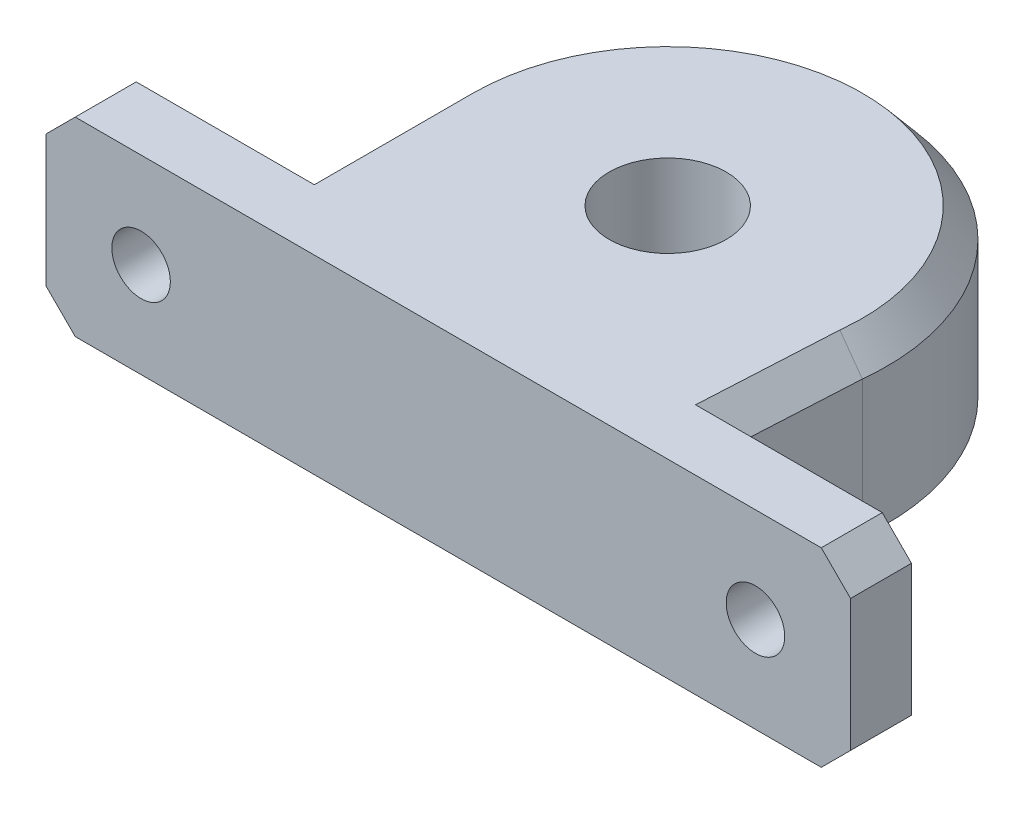
SolidWorks part; units mm, degrees
ref_plane "Płaszczyzna przednia" through (0, 0, 0) normal (0, 0, 1) x (1, 0, 0)
ref_plane "Płaszczyzna górna" through (0, 0, 0) normal (0, 1, 0) x (1, 0, 0)
ref_plane "Płaszczyzna prawa" through (0, 0, 0) normal (1, 0, 0) x (0, 0, -1)
sketch "Szkic1" plane through (0, 0, 0) normal (0, 1, 0) x (1, 0, 0)
  circle A0 centre (0, 15) radius 15
  circle A1 centre (0, 15) radius 4
extrude "Dodanie-wyciągnięcie1" add sketch "Szkic1" along normal blind 13
sketch "Szkic2" plane through (0, 0, 0) normal (0, -1, 0) x (1, 0, 0)
  line L0 (0, 0) -> (27.5, 0)
  line L1 (27.5, 0) -> (27.5, -4.1663)
  line L2 (27.5, -4.1663) -> (14.4188, -4.1663)
  line L3 (14.4188, -4.1663) -> (15, -15)
  line L4 (15, -15) -> (0, -4.1663)
  line L5 (0, -4.1663) -> (-15, -15)
  line L6 (-15, -15) -> (-15, -4.1663)
  line L7 (-15, -4.1663) -> (-27.5, -4.1663)
  line L8 (-27.5, -4.1663) -> (-27.5, 0)
  line L9 (-27.5, 0) -> (0, 0)
  circle A0 centre (0, -15) radius 15 construction
  point P3 (0, 0)
  point P14 (0, 0)
extrude "Dodanie-wyciągnięcie2" add sketch "Szkic2" against normal blind 13
chamfer "Sfazowanie1" distance 2 angle 40 4 edges at (-15, 0, -9.5832) (-15, 13, -9.5832) (0.8036, 0, -29.9785) (0.8036, 13, -29.9785)
sketch "Szkic3" plane through (0, 0, 0) normal (0, 0, 1) x (1, 0, 0)
  circle A0 centre (-21, 6.5) radius 2
  circle A1 centre (21, 6.5) radius 2
  point P4 (0, 0)
  point P5 (0, 0)
  point P6 (0, 0)
extrude "Wytnij-wyciągnięcie1" cut sketch "Szkic3" against normal up to next
chamfer "Sfazowanie2" distance 2 angle 45 4 edges at (27.5, 0, -2.0832) (27.5, 13, -2.0832) (-27.5, 0, -2.0832) (-27.5, 13, -2.0832)
